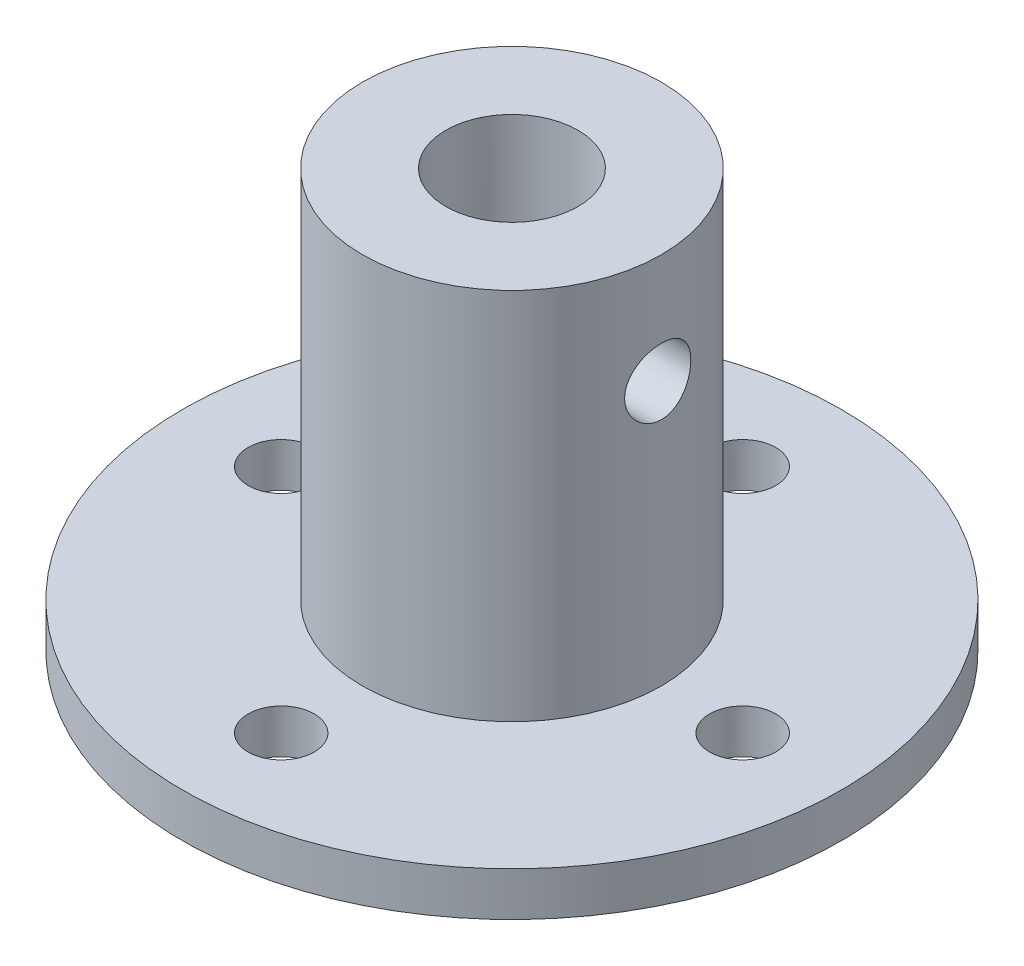
SolidWorks part; units mm, degrees
ref_plane "Front" through (0, 0, 0) normal (0, 0, 1) x (1, 0, 0)
ref_plane "Top" through (0, 0, 0) normal (0, 1, 0) x (1, 0, 0)
ref_plane "Right" through (0, 0, 0) normal (1, 0, 0) x (0, 0, -1)
sketch "Sketch1" plane through (0, 0, 0) normal (1, 0, 0) x (0, 0, -1)
  line L0 (0, 0) -> (0, 16.6624) construction
  line L1 (2.3876, 0) -> (2.3876, 16.6624)
  line L2 (2.3876, 16.6624) -> (5.3975, 16.6624)
  line L3 (5.3975, 16.6624) -> (5.3975, 3.175)
  line L4 (5.3975, 3.175) -> (11.8999, 3.175)
  line L5 (11.8999, 3.175) -> (11.8999, 1.5875)
  line L6 (11.8999, 1.5875) -> (3.9243, 1.5875)
  line L7 (3.9243, 1.5875) -> (3.9243, 0)
  line L8 (3.9243, 0) -> (2.3876, 0)
  line L9 (0, 0) -> (0, 12.7)
  circle A0 centre (0, 12.7) radius 1.1938
revolve "Revolve1" add sketch "Sketch1" angle 360 about L0 region at (0, 7.578, -4.7061)
extrude "Cut-Extrude1" cut sketch "Sketch1<5>" against normal through all and the other way through all contours A0
sketch "Sketch1<5>" plane through (0, 0, 0) normal (1, 0, 0) x (0, 0, -1) same geometry as "Sketch1"
sketch "Sketch2" plane through (0, 0, 0) normal (0, 1, 0) x (1, 0, 0)
  circle A1 centre (-8.3312, 0) radius 1.1938
  circle A2 centre (0, 8.3312) radius 1.1938
  circle A3 centre (0, -8.3312) radius 1.1938
  circle A4 centre (8.3312, 0) radius 1.1938
extrude "Cut-Extrude2" cut sketch "Sketch2" along normal through all contours A1 | A2 | A4 | A3
